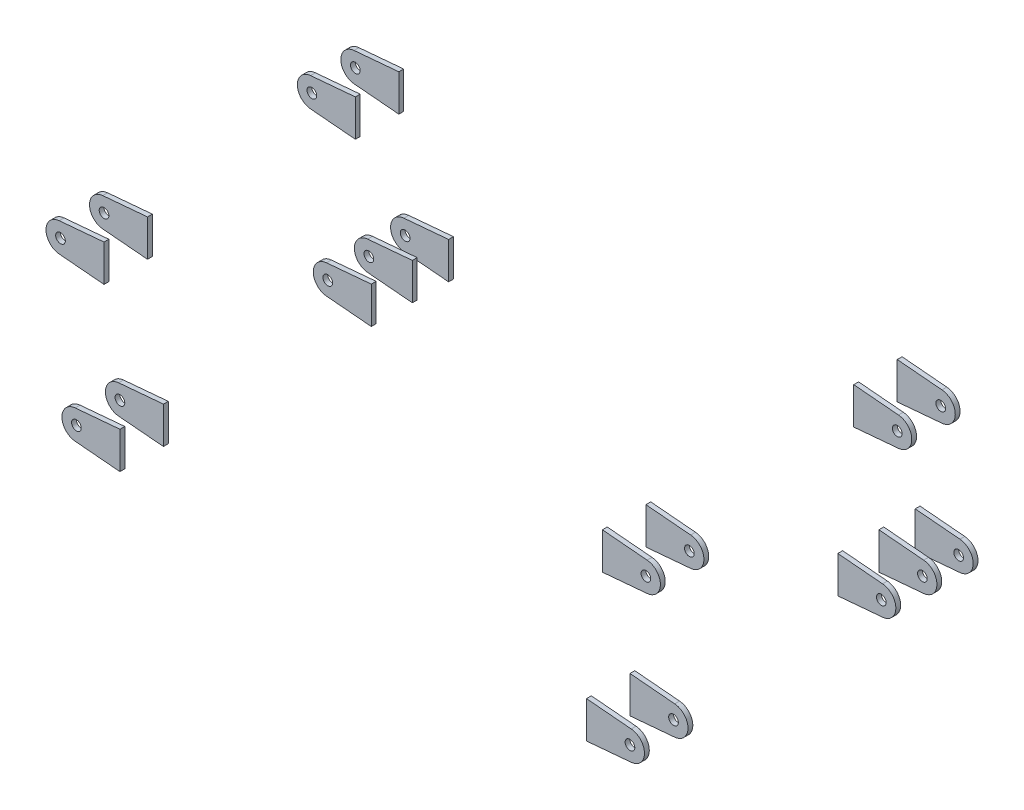
SolidWorks part; units mm, degrees
ref_plane "Front Plane" through (0, 0, 0) normal (0, 0, 1) x (1, 0, 0)
ref_plane "Top Plane" through (0, 0, 0) normal (0, 1, 0) x (1, 0, 0)
ref_plane "Right Plane" through (0, 0, 0) normal (1, 0, 0) x (0, 0, -1)
ref_plane "Plane4" through (0, 0, -1495) normal (0, 0, 1) x (1, 0, 0)
ref_plane "Plane5" through (0, 0, -1755) normal (0, 0, 1) x (1, 0, 0)
ref_plane "Plane7" through (0, 0, -1755) normal (0, 0, 1) x (1, 0, 0)
ref_plane "Plane8" through (0, 0, -1795) normal (0, 0, 1) x (1, 0, 0)
sketch "Sketch1" plane through (0, 0, -1495) normal (0, 0, 1) x (1, 0, 0)
  line L0 (304.0787, 356.998) -> (257.7695, 361.0552)
  line L1 (257.7695, 361.0552) -> (257.7695, 323.0552)
  line L2 (257.7695, 323.0552) -> (304.0787, 327.1124)
  circle A0 centre (302.7695, 342.0552) radius 5
  circle A1 centre (302.7695, 342.0552) radius 15
  point P9 (257.7695, 342.0552)
  dimension "D1" = 30
  dimension "D2" = 10
  dimension "D3" = 38
extrude "Boss-Extrude1" add sketch "Sketch1" along normal blind 5 from offset 20 contours A1 A0 | A1 L0 L1 L2 region at (274.3065, 342.0552, -1495) region at (313.5165, 351.9018, -1495)
extrude "Boss-Extrude2" add sketch "Sketch1<3>" against normal blind 5 from offset 20 separate body contours A1 A0 | A1 L0 L1 L2 region at (274.3065, 342.0552, -1495) region at (313.5165, 351.9018, -1495) offset against normal yes
sketch "Sketch1<3>" plane through (0, 0, -1495) normal (0, 0, 1) x (1, 0, 0) same geometry as "Sketch1"
sketch "Sketch2" plane through (0, 0, -1755) normal (0, 0, 1) x (1, 0, 0)
  line L0 (304.0787, 356.998) -> (257.7695, 361.0552) construction
  line L1 (257.7695, 361.0552) -> (257.7695, 323.0552) construction
  line L2 (257.7695, 323.0552) -> (304.0787, 327.1124) construction
  line L3 (304.0787, 356.998) -> (257.7695, 361.0552)
  line L4 (257.7695, 361.0552) -> (257.7695, 323.0552)
  line L5 (257.7695, 323.0552) -> (304.0787, 327.1124)
  circle A1 centre (302.7695, 342.0552) radius 15
  circle A2 centre (302.7695, 342.0552) radius 15
  circle A3 centre (302.7695, 342.0552) radius 5
  circle A4 centre (302.7695, 342.0552) radius 5
  dimension "D1" = 0
  dimension "D2" = 0
extrude "Boss-Extrude3" add sketch "Sketch2" against normal blind 5 from offset 20 separate body contours A2 L3 L4 L5 | A2 A4 region at (274.3065, 342.0552, -1755) region at (313.5165, 351.9018, -1755) offset against normal yes
extrude "Boss-Extrude4" add sketch "Sketch2<4>" along normal blind 5 from offset 20 separate body contours A2 A4 | A2 L3 L4 L5 region at (274.3065, 342.0552, -1755) region at (313.5165, 351.9018, -1755)
sketch "Sketch2<4>" plane through (0, 0, -1755) normal (0, 0, 1) x (1, 0, 0) same geometry as "Sketch2"
ref_plane "Plane6" through (0, 0, -1495) normal (0, 0, 1) x (1, 0, 0)
sketch "Sketch3" plane through (0, 0, -1495) normal (0, 0, 1) x (1, 0, 0)
  line L0 (241.3, 163.578) -> (241.3, 201.578)
  line L1 (287.6092, 197.5207) -> (241.3, 201.578)
  line L2 (287.6092, 167.6352) -> (241.3, 163.578)
  circle A0 centre (286.3, 182.578) radius 5
  circle A1 centre (286.3, 182.578) radius 15
  point P4 (241.3, 182.578)
  dimension "D1" = 38
  dimension "D2" = 10
  dimension "D3" = 30
extrude "Boss-Extrude5" add sketch "Sketch3" along normal blind 5 from offset 20 separate body contours A1 A0 | A1 L1 L0 L2 region at (257.837, 182.578, -1495) region at (271.7243, 182.578, -1495)
extrude "Boss-Extrude6" add sketch "Sketch3<3>" against normal blind 5 from offset 20 separate body contours A1 L1 L0 L2 | A1 A0 region at (257.837, 182.578, -1495) region at (271.7243, 182.578, -1495) offset against normal yes
sketch "Sketch3<3>" plane through (0, 0, -1495) normal (0, 0, 1) x (1, 0, 0) same geometry as "Sketch3"
sketch "Sketch4" plane through (0, 0, -1755) normal (0, 0, 1) x (1, 0, 0)
  line L0 (287.6092, 197.5207) -> (241.3, 201.578) construction
  line L1 (241.3, 163.578) -> (241.3, 201.578) construction
  line L2 (287.6092, 167.6352) -> (241.3, 163.578) construction
  line L3 (287.6092, 197.5207) -> (241.3, 201.578)
  line L4 (241.3, 163.578) -> (241.3, 201.578)
  line L5 (287.6092, 167.6352) -> (241.3, 163.578)
  circle A1 centre (286.3, 182.578) radius 15
  circle A2 centre (286.3, 182.578) radius 15
  circle A3 centre (286.3, 182.578) radius 5
  circle A4 centre (286.3, 182.578) radius 5
  dimension "D1" = 0
  dimension "D2" = 0
extrude "Boss-Extrude7" add sketch "Sketch4" along normal blind 5 from offset 20 separate body contours A2 L3 L4 L5 | A2 A4 region at (257.837, 182.578, -1755) region at (297.047, 192.4245, -1755)
extrude "Boss-Extrude8" add sketch "Sketch4<3>" against normal mid plane 5 from offset 20 separate body contours A2 L3 L4 L5 | A2 A4 region at (257.837, 182.578, -1755) region at (297.047, 192.4245, -1755) offset against normal yes
sketch "Sketch4<3>" plane through (0, 0, -1755) normal (0, 0, 1) x (1, 0, 0) same geometry as "Sketch4"
sketch "Sketch5" plane through (0, 0, -1795) normal (0, 0, 1) x (1, 0, 0)
  line L0 (287.6092, 197.5207) -> (241.3, 201.578) construction
  line L1 (241.3, 163.578) -> (241.3, 201.578) construction
  line L2 (287.6092, 167.6352) -> (241.3, 163.578) construction
  line L3 (287.6092, 197.5207) -> (241.3, 201.578)
  line L4 (241.3, 163.578) -> (241.3, 201.578)
  line L5 (287.6092, 167.6352) -> (241.3, 163.578)
  circle A1 centre (286.3, 182.578) radius 5
  circle A2 centre (286.3, 182.578) radius 5
  circle A3 centre (286.3, 182.578) radius 15
  circle A4 centre (286.3, 182.578) radius 15
  dimension "D1" = 0
  dimension "D2" = 0
extrude "Boss-Extrude9" add sketch "Sketch5" against normal blind 5 from offset 15 separate body contours A4 L3 L4 L5 | A4 A2 region at (257.837, 182.578, -1795) region at (297.047, 192.4245, -1795) offset against normal yes
mirror "Mirror1" about plane through (0, 0, 0) normal (1, 0, 0) of bodies 101 102 104 103 105 106 107 108 109
